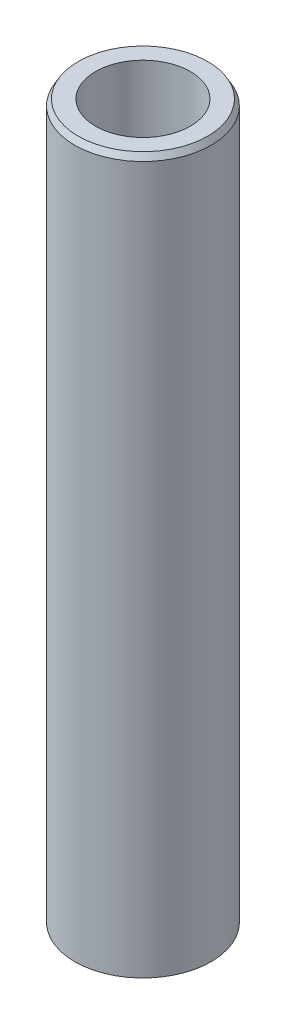
SolidWorks part; units mm, degrees
ref_plane "Front Plane" through (0, 0, 0) normal (0, 0, 1) x (1, 0, 0)
ref_plane "Top Plane" through (0, 0, 0) normal (0, 1, 0) x (1, 0, 0)
ref_plane "Right Plane" through (0, 0, 0) normal (1, 0, 0) x (0, 0, -1)
sketch "Sketch1" plane through (0, 0, 0) normal (0, 1, 0) x (1, 0, 0)
  circle A0 centre (0, 0) radius 10
  dimension "SHAFT_OD" = 20
extrude "Boss-Extrude1" add sketch "Sketch1" along normal blind 105.0424
sketch "Sketch2" plane through (0, 0, 0) normal (0, 1, 0) x (1, 0, 0)
  circle A0 centre (0, 0) radius 6.9478
  dimension "BORE_D" = 13.8956
extrude "Cut-Extrude1" cut sketch "Sketch2" along normal through all
chamfer "Chamfer1" distance 0.888 angle 30 2 edges at (0, 105.0424, 10) (0, 0, 10) first distance on face at (0, 105.0424, 10) first distance on face at (0, 0, 6.9478)
